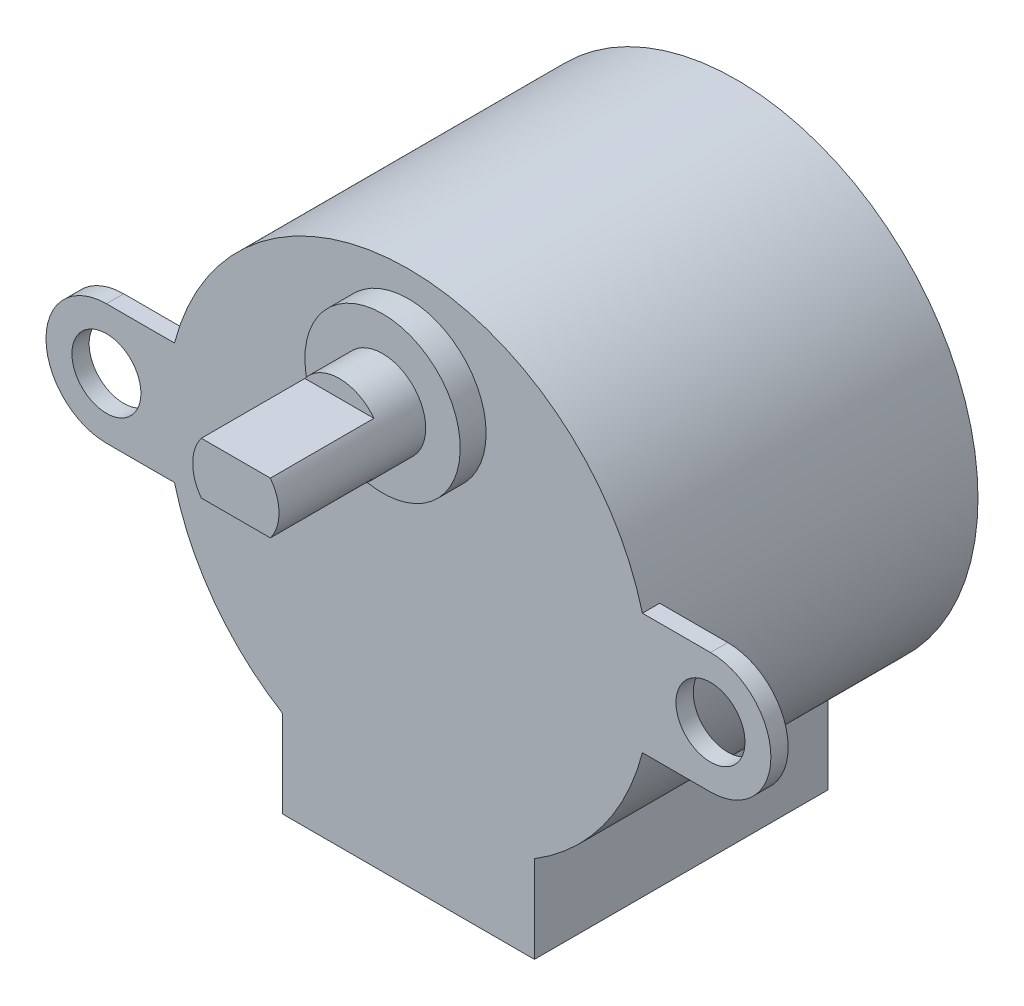
SolidWorks part; units mm, degrees
ref_plane "Front Plane" through (0, 0, 0) normal (0, 0, 1) x (1, 0, 0)
ref_plane "Top Plane" through (0, 0, 0) normal (0, 1, 0) x (1, 0, 0)
ref_plane "Right Plane" through (0, 0, 0) normal (1, 0, 0) x (0, 0, -1)
sketch "Sketch2" plane through (0, 0, 0) normal (0, 0, 1) x (1, 0, 0)
  line L0 (-7.3, -11.9461) -> (-7.3, -17)
  line L1 (-7.3, -17) -> (7.3, -17)
  line L2 (7.3, -17) -> (7.3, -11.9461)
  line L3 (0, -17) -> (0, 0) construction
  circle A0 centre (0, 0) radius 14
  dimension "D1" = 28
  dimension "D2" = 14.6
  dimension "D3" = 17
extrude "Boss-Extrude1" add sketch "Sketch2" against normal blind 19 contours A0 region at (0, 0, 0)
extrude "Boss-Extrude2" add sketch "Sketch2<3>" against normal blind 17 contours L3 L1 L2 A0 | L1 L3 A0 L0 region at (-3.9854, -15.1184, 0) region at (3.9854, -15.1184, 0)
sketch "Sketch2<3>" plane through (0, 0, 0) normal (0, 0, 1) x (1, 0, 0) same geometry as "Sketch2"
sketch "Sketch4" plane through (0, 0, 0) normal (1, 0, 0) x (0, 0, -1)
  line L0 (0, 14) -> (0, -11.9461) construction
  line L1 (0, 14) -> (0, -11.9461) construction
  line L2 (0, 8) -> (-10, 8) construction
  line L3 (-10, 8) -> (-10, 10.5)
  line L6 (-10, 10.5) -> (-1.5, 10.5)
  line L7 (-1.5, 10.5) -> (-1.5, 12.5)
  line L8 (-1.5, 12.5) -> (0, 12.5)
  line L9 (0, 12.5) -> (0, 8)
  line L10 (0, 8) -> (-10, 8)
  dimension "D2" = 1.5
  dimension "D3" = 10
  dimension "D4" = 9
  dimension "D6" = 5
  dimension "D7" = 8
revolve "Revolve1" add sketch "Sketch4" angle 360 about L10
sketch "Sketch5" plane through (0, 0, 10) normal (0, 0, 1) x (1, 0, 0)
  line L0 (-2, 9.5) -> (2, 9.5)
  line L1 (-2.5, 8) -> (0, 8) construction
  line L2 (-2, 6.5) -> (2, 6.5)
  circle A1 centre (0, 8) radius 2.5
  circle A2 centre (0, 8) radius 2.5
  circle M5 centre (0, 8) radius 2.5
  dimension "D2" = 3
  dimension "D1" = 0
extrude "Cut-Extrude1" cut sketch "Sketch5" against normal blind 6 contours L0 M5 | L2 M5 region at (0, 9.9078, 10) region at (0, 6.0922, 10)
sketch "Sketch6" plane through (0, 0, 0) normal (0, 0, 1) x (1, 0, 0)
  line L0 (-17.5, 3.5) -> (-13.5554, 3.5)
  line L1 (-17.5, -3.5) -> (-13.5554, -3.5)
  line L2 (0, 0) -> (0, -17) construction
  line L3 (17.5, -3.5) -> (13.5554, -3.5)
  line L4 (17.5, 3.5) -> (13.5554, 3.5)
  line L5 (-7.3, -11.9461) -> (-7.3, -17)
  line L6 (-7.3, -17) -> (7.3, -17)
  line L7 (7.3, -17) -> (7.3, -11.9461)
  line L8 (-7.3, -11.9461) -> (-7.3, -17) construction
  line L9 (-7.3, -17) -> (7.3, -17) construction
  line L10 (7.3, -17) -> (7.3, -11.9461) construction
  line L11 (-17.5, 0) -> (0, 0) construction
  circle A0 centre (-17.5, 0) radius 2
  arc A1 (-17.5, 3.5) -> (-17.5, -3.5) centre (-17.5, 0) ccw
  arc A2 (7.3, -11.9461) -> (-7.3, -11.9461) centre (0, 0) ccw construction
  arc A3 (-17.5, -3.5) -> (-17.5, 3.5) centre (-17.5, 0) ccw construction
  arc A4 (7.3, -11.9461) -> (-13.5554, 3.5) centre (0, 0) ccw construction
  arc A5 (7.3, -11.9461) -> (-7.3, -11.9461) centre (0, 0) ccw
  arc A6 (-13.5554, 3.5) -> (-13.5554, -3.5) centre (0, 0) ccw
  arc A7 (-13.5554, -3.5) -> (-7.3, -11.9461) centre (0, 0) ccw construction
  arc A8 (17.5, -3.5) -> (17.5, 3.5) centre (17.5, 0) cw construction
  arc A9 (13.5554, 3.5) -> (13.5554, -3.5) centre (0, 0) cw
  arc A10 (17.5, 3.5) -> (17.5, -3.5) centre (17.5, 0) cw
  circle A11 centre (17.5, 0) radius 2
  dimension "D1" = 0
  dimension "D2" = 3.5
  dimension "D4" = 4
  dimension "D3" = 35
extrude "Boss-Extrude3" add sketch "Sketch6" against normal blind 1
